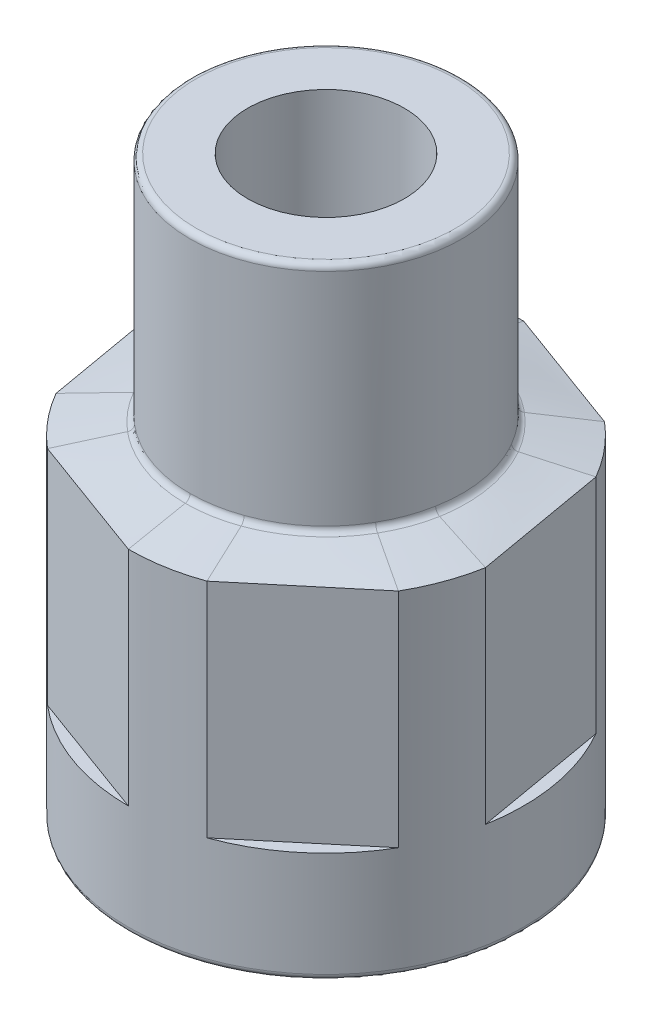
SolidWorks part; units mm, degrees
ref_plane "Спереди" through (0, 0, 0) normal (0, 0, 1) x (1, 0, 0)
ref_plane "Сверху" through (0, 0, 0) normal (0, 1, 0) x (1, 0, 0)
ref_plane "Справа" through (0, 0, 0) normal (1, 0, 0) x (0, 0, -1)
sketch "Эскиз1" plane through (0, 0, 0) normal (0, 1, 0) x (1, 0, 0)
  circle A0 centre (0, 0) radius 11
  dimension "D1" = 22
ref_plane "Плоскость1" through (0, -18.75, 0) normal (0, 1, 0) x (1, 0, 0)
sketch "Эскиз2" plane through (0, -18.75, 0) normal (0, 1, 0) x (1, 0, 0)
  circle A2 centre (0, 0) radius 11
  dimension "D1" = 22
loft "По сечениям1" add profiles "Эскиз2", "Эскиз1" connector at (-7.995, -18.75, -7.5552) connector at (-8.0065, 0, -7.5429)
cosmetic thread "Условное изображение резьбы3" parameters "D1"=51.718, "D2"=20.344
sketch "Эскиз3" plane through (0, 0, 0) normal (0, 1, 0) x (1, 0, 0)
  circle A0 centre (0, 0) radius 6.35
  dimension "D1" = 12.7
extrude "Вырез-Вытянуть1" cut sketch "Эскиз3" against normal blind 12
sketch "Эскиз4" plane through (0, -12, 0) normal (0, 1, 0) x (1, 0, 0)
  circle A0 centre (0, 0) radius 4.85
  circle A1 centre (0, 0) radius 6.35 construction
  dimension "D1" = 1.5
extrude "Вырез-Вытянуть2" cut sketch "Эскиз4" against normal through all
ref_plane "Плоскость2" through (0, -3.5, 0) normal (0, 1, 0) x (1, 0, 0)
ref_plane "Плоскость3" through (0, -19.75, 0) normal (0, 1, 0) x (1, 0, 0)
sketch "Эскиз6" plane through (0, -19.75, 0) normal (0, 1, 0) x (1, 0, 0)
  line L1 (-5.4169, 15.0551) -> (-13.8564, 8)
  line L2 (-15.7466, 2.8364) -> (-13.8564, -8)
  line L3 (-10.3297, -12.2187) -> (0, -16)
  line L4 (5.4169, -15.0551) -> (13.8564, -8)
  line L5 (15.7466, -2.8364) -> (13.8564, 8)
  line L6 (10.3297, 12.2188) -> (0, 16)
  arc A0 (-13.8564, 8) -> (-15.7466, 2.8364) centre (0, 0) ccw
  circle A1 centre (0, 0) radius 15.025 construction
  arc A2 (-13.8564, -8) -> (-10.3297, -12.2187) centre (0, 0) ccw
  arc A3 (0, 16) -> (-5.4169, 15.0551) centre (0, 0) ccw
  arc A4 (13.8564, 8) -> (10.3297, 12.2188) centre (0, 0) ccw
  arc A5 (13.8564, -8) -> (15.7466, -2.8364) centre (0, 0) ccw
  arc A6 (0, -16) -> (5.4169, -15.0551) centre (0, 0) ccw
  point P3 (-13.8564, 8)
  point P11 (-5.4169, 15.0551)
  dimension "D1" = 32
  dimension "D2" = 11
ref_plane "Плоскость4" through (0, -37.75, 0) normal (0, 1, 0) x (1, 0, 0)
sketch "Эскиз7" plane through (0, -37.75, 0) normal (0, 1, 0) x (1, 0, 0)
  line L0 (-10.3297, -12.2187) -> (0, -16) construction
  line L1 (5.4169, -15.0551) -> (13.8564, -8) construction
  line L2 (15.7466, -2.8364) -> (13.8564, 8) construction
  line L3 (10.3297, 12.2188) -> (0, 16) construction
  line L4 (-5.4169, 15.0551) -> (-13.8564, 8) construction
  line L5 (-15.7466, 2.8364) -> (-13.8564, -8) construction
  line L6 (-10.3297, -12.2187) -> (0, -16)
  line L7 (5.4169, -15.0551) -> (13.8564, -8)
  line L8 (15.7466, -2.8364) -> (13.8564, 8)
  line L9 (10.3297, 12.2188) -> (0, 16)
  line L10 (-5.4169, 15.0551) -> (-13.8564, 8)
  line L11 (-15.7466, 2.8364) -> (-13.8564, -8)
  arc A0 (0, -16) -> (5.4169, -15.0551) centre (0, 0) ccw construction
  arc A1 (13.8564, -8) -> (15.7466, -2.8364) centre (0, 0) ccw construction
  arc A2 (13.8564, 8) -> (10.3297, 12.2188) centre (0, 0) ccw construction
  arc A3 (0, 16) -> (-5.4169, 15.0551) centre (0, 0) ccw construction
  arc A4 (-13.8564, 8) -> (-15.7466, 2.8364) centre (0, 0) ccw construction
  arc A5 (-13.8564, -8) -> (-10.3297, -12.2187) centre (0, 0) ccw construction
  arc A6 (0, -16) -> (5.4169, -15.0551) centre (0, 0) ccw
  arc A7 (13.8564, -8) -> (15.7466, -2.8364) centre (0, 0) ccw
  arc A8 (13.8564, 8) -> (10.3297, 12.2188) centre (0, 0) ccw
  arc A9 (0, 16) -> (-5.4169, 15.0551) centre (0, 0) ccw
  arc A10 (-13.8564, 8) -> (-15.7466, 2.8364) centre (0, 0) ccw
  arc A11 (-13.8564, -8) -> (-10.3297, -12.2187) centre (0, 0) ccw
loft "По сечениям2" add profiles "Эскиз6", "Эскиз2<3>" connector at (15.7466, -19.75, 2.8364) connector at (-8.4845, -18.75, -7.001)
sketch "Эскиз2<3>" plane through (0, -18.75, 0) normal (0, 1, 0) x (1, 0, 0) same geometry as "Эскиз2"
loft "По сечениям3" add profiles "Эскиз7", "Эскиз6<3>" connector at (-13.8564, -37.75, 8) connector at (-13.8564, -19.75, 8)
sketch "Эскиз6<3>" plane through (0, -19.75, 0) normal (0, 1, 0) x (1, 0, 0) same geometry as "Эскиз6"
sketch "Эскиз8" plane through (0, -37.75, 0) normal (0, 1, 0) x (1, 0, 0)
  circle A0 centre (0, 0) radius 16
  dimension "D1" = 32
ref_plane "Плоскость5" through (0, -46.75, 0) normal (0, 1, 0) x (1, 0, 0)
sketch "Эскиз9" plane through (0, -46.75, 0) normal (0, 1, 0) x (1, 0, 0)
  circle A0 centre (0, 0) radius 16 construction
  circle A1 centre (0, 0) radius 16
extrude "Бобышка-Вытянуть1" add sketch "Эскиз8" against normal blind 9 contours A0
ref_plane "Плоскость6" through (0, -47.75, 0) normal (0, 1, 0) x (1, 0, 0)
sketch "Эскиз10" plane through (0, -47.75, 0) normal (0, 1, 0) x (1, 0, 0)
  circle A0 centre (0, 0) radius 13.9
  dimension "D1" = 27.8
extrude "Бобышка-Вытянуть2" add sketch "Эскиз10" along normal blind 1
sketch "Эскиз11" plane through (0, -47.75, 0) normal (0, -1, 0) x (1, 0, 0)
  circle A0 centre (0, 0) radius 10
  dimension "D1" = 20
extrude "Вырез-Вытянуть3" cut sketch "Эскиз11" against normal blind 20
cosmetic thread "Условное изображение резьбы4" parameters "D2"=22
sketch "Эскиз12" plane through (0, -27.75, 0) normal (0, -1, 0) x (1, 0, 0)
  circle A0 centre (0, 0) radius 7.75
  dimension "D1" = 15.5
ref_plane "Плоскость7" through (0, -18.75, 0) normal (0, 1, 0) x (1, 0, 0)
extrude "Вырез-Вытянуть4" cut sketch "Эскиз12" against normal up to surface (9 mm away) up to plane "Плоскость7"
fillet "Скругление1" radius 0.5 12 edges
sketch "Эскиз13" plane through (0, -3.5, 0) normal (0, 1, 0) x (1, 0, 0)
  circle A0 centre (0, 0) radius 11 construction
  circle A1 centre (0, 0) radius 11
fillet "Скругление2" radius 0.5 1 edges at (0, -46.75, 16)
fillet "Скругление3" radius 0.2 1 edges at (0, -46.75, 13.9)
fillet "Скругление4" radius 0.2 1 edges at (0, -47.75, 13.9)
fillet "Скругление5" radius 0.5 1 edges at (0, 0, 11)
